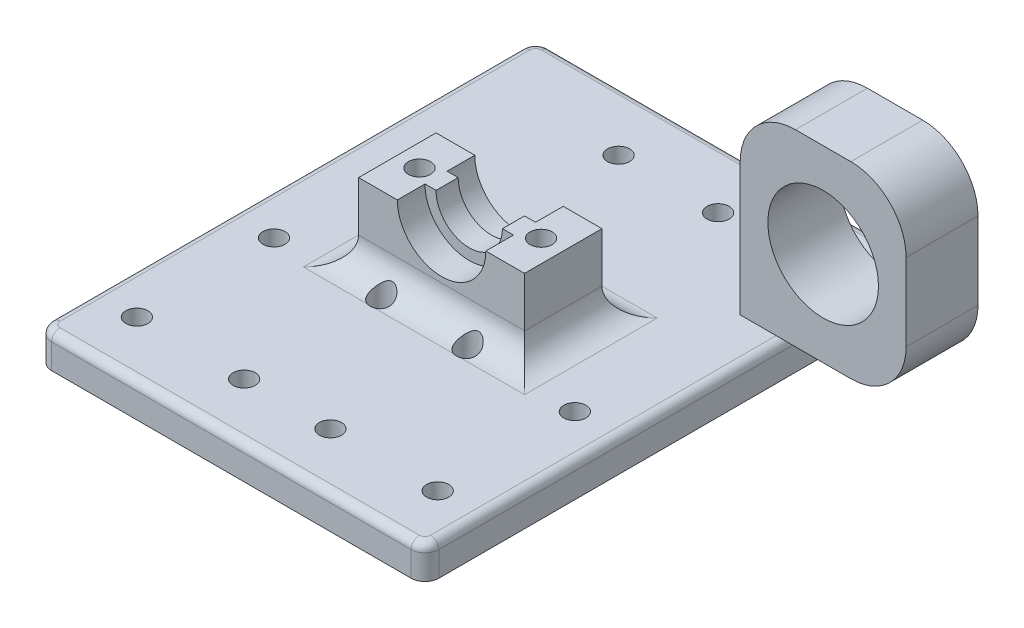
SolidWorks part; units mm, degrees
ref_plane "Front Plane" through (0, 0, 0) normal (0, 0, 1) x (1, 0, 0)
ref_plane "Top Plane" through (0, 0, 0) normal (0, 1, 0) x (1, 0, 0)
ref_plane "Right Plane" through (0, 0, 0) normal (1, 0, 0) x (0, 0, -1)
sketch "Sketch1" plane through (0, 0, 0) normal (0, 1, 0) x (1, 0, 0)
  line L0 (-8.0156, -1.4008) -> (61.9844, -1.4008)
  line L1 (-8.0156, 43.5992) -> (61.9844, 43.5992)
  line L2 (-8.0156, 43.5992) -> (-8.0156, -46.4008)
  line L3 (-8.0156, -46.4008) -> (61.9844, -46.4008)
  line L4 (61.9844, 43.5992) -> (61.9844, -46.4008)
  line L5 (26.9844, 43.5992) -> (26.9844, -46.4008)
  line L6 (9.4844, -1.4008) -> (9.4844, -46.4008)
  line L7 (-8.0156, -23.9008) -> (61.9844, -23.9008)
  circle A0 centre (17.9844, 32.5992) radius 3
  circle A1 centre (17.9844, 32.5992) radius 2
  circle A2 centre (18.095, 8.5992) radius 3
  circle A3 centre (18.095, 8.5992) radius 2
  circle A4 centre (35.8739, 8.5992) radius 2
  circle A5 centre (35.8739, 8.5992) radius 3
  circle A6 centre (35.9844, 32.5992) radius 2
  circle A7 centre (35.9844, 32.5992) radius 3
  circle A8 centre (19.1844, -11.5008) radius 2
  circle A9 centre (19.1844, -11.5008) radius 3
  circle A10 centre (-0.2156, -11.5008) radius 3
  circle A11 centre (-0.2156, -11.5008) radius 2
  circle A12 centre (-0.2156, -36.3008) radius 2
  circle A13 centre (19.1844, -36.3008) radius 3
  circle A14 centre (19.1844, -36.3008) radius 2
  circle A15 centre (-0.2156, -36.3008) radius 3
  circle A16 centre (54.1844, -36.3008) radius 2
  circle A17 centre (54.1844, -36.3008) radius 3
  circle A18 centre (34.7844, -36.3008) radius 2
  circle A19 centre (34.7844, -36.3008) radius 3
  circle A20 centre (34.7844, -11.5008) radius 3
  circle A21 centre (34.7844, -11.5008) radius 2
  circle A22 centre (54.1844, -11.5008) radius 2
  circle A23 centre (54.1844, -11.5008) radius 3
  dimension "D3" = 9
  dimension "D1" = 90
  dimension "D2" = 70
  dimension "D4" = 11
  dimension "D5" = 24
  dimension "D6" = 10.1
  dimension "D7" = 7.8
  dimension "D8" = 17.5
  dimension "D9" = 22.5
extrude "Boss-Extrude1" add sketch "Sketch1" along normal blind 6 contours L5 L1 L2 L0 A2 A0 | L1 L5 L0 L4 A5 A7 | A7 A6 | A0 A1 | A2 A3 | A5 A4 | L7 L6 L3 L5 A13 | L6 L7 L5 L0 A9 | L2 L7 L6 L0 A10 | L5 L7 L4 L0 A20 A23 | L7 L5 L3 L4 A17 A19 | L7 L2 L3 L6 A15 | A10 A11 | A9 A8 | A20 A21 | A23 A22 | A17 A16 | A13 A14 | A15 A12 | A19 | A18 region at (9.1658, 0, -21.1178) region at (0.7344, 0, 1.6858) region at (18.2344, 0, 1.6858) region at (0.7344, 0, 24.1858) region at (44.803, 0, -21.1178) region at (44.4844, 0, 12.7397) region at (18.2344, 0, 24.1858) region at (44.4844, 0, 35.0618) region at (15.0693, 0, -32.5992) region at (15.1799, 0, -8.5992) region at (32.9587, 0, -8.5992) region at (33.0693, 0, -32.5992) region at (16.2693, 0, 11.5008) region at (-3.1307, 0, 11.5008) region at (16.2693, 0, 36.3008) region at (-3.1307, 0, 36.3008) region at (51.2693, 0, 36.3008) region at (31.8693, 0, 11.5008) region at (51.2693, 0, 11.5008)
sketch "Sketch3" plane through (0, 6, 0) normal (0, 1, 0) x (1, 0, 0)
  line L0 (26.9844, 43.5992) -> (26.9844, -46.4008)
  line L1 (11.9844, 5.5992) -> (41.9844, 5.5992)
  line L2 (11.9844, 5.5992) -> (11.9844, -8.4008)
  line L3 (11.9844, -8.4008) -> (41.9844, -8.4008)
  line L4 (41.9844, 5.5992) -> (41.9844, -8.4008)
  line L5 (-8.0156, 43.5992) -> (61.9844, 43.5992) construction
  line L6 (-8.0156, -46.4008) -> (61.9844, -46.4008) construction
  line L7 (-8.0156, -1.4008) -> (61.9844, -1.4008)
  line L8 (-8.0156, 43.5992) -> (-8.0156, -46.4008) construction
  line L9 (61.9844, 43.5992) -> (61.9844, -46.4008) construction
  dimension "D1" = 14
  dimension "D2" = 30
  dimension "D3" = 7
  dimension "D4" = 15
extrude "Boss-Extrude2" add sketch "Sketch3" along normal blind 14 contours L2 L7 L0 L1 | L0 L7 L4 L1 | L7 L0 L3 L4 | L7 L2 L3 L0 region at (34.4844, 6, -2.0992) region at (19.4844, 6, -2.0992) region at (34.4844, 6, 4.9008) region at (19.4844, 6, 4.9008)
fillet "Fillet1" radius 2.5 4 edges at (-8.0156, 3, -43.5992) (61.9844, 3, -43.5992) (61.9844, 3, 46.4008) (-8.0156, 3, 46.4008)
fillet "Fillet2" radius 1.5 8 edges at (26.9844, 6, -43.5992) (-7.2833, 6, 45.6685) (61.2522, 6, 45.6685) (26.9844, 6, 46.4008) (61.2522, 6, -42.867) (61.9844, 6, 1.4008) (-7.2833, 6, -42.867) (-8.0156, 6, 1.4008)
sketch "Sketch4" plane through (0, 20, 0) normal (0, 1, 0) x (1, 0, 0)
  line L0 (26.9844, 42.0992) -> (26.9844, -44.9008)
  line L1 (59.4844, 42.0992) -> (-5.5156, 42.0992) construction
  line L2 (-5.5156, -44.9008) -> (59.4844, -44.9008) construction
  line L3 (-6.5156, -1.4008) -> (60.4844, -1.4008)
  line L4 (-6.5156, 41.0992) -> (-6.5156, -43.9008) construction
  line L5 (60.4844, -43.9008) -> (60.4844, 41.0992) construction
  circle A0 centre (15.9844, -1.4008) radius 2
  circle A1 centre (37.9844, -1.4008) radius 2
  dimension "D1" = 11
extrude "Cut-Extrude1" cut sketch "Sketch4" against normal blind 22 contours L3 A0 | L3 A0 | A1 L3 | A1 L3 region at (15.9844, 20, 0.552) region at (37.9844, 20, 0.552) region at (37.9844, 20, 2.2496) region at (15.9844, 20, 2.2496)
sketch "Sketch5" plane through (0, 0, -5.5992) normal (0, 0, -1) x (-1, 0, 0)
  line L0 (-11.9844, 20) -> (-41.9844, 20) construction
  line L1 (-34.9844, 20) -> (-18.9844, 20)
  circle A0 centre (-26.9844, 20) radius 8
  circle A1 centre (-26.9844, 20) radius 6
extrude "Cut-Extrude2" cut sketch "Sketch5" against normal blind 22 contours A1
sketch "Sketch6" plane through (0, 0, -5.5992) normal (0, 0, -1) x (-1, 0, 0)
  line L0 (-18.9844, 20) -> (-34.9844, 20)
  circle A0 centre (-26.9844, 20) radius 8
  circle A1 centre (-26.9844, 20) radius 6
  circle A2 centre (-26.9844, 20) radius 6
  circle A3 centre (-26.9844, 20) radius 8
  arc M1 (-20.9844, 20) -> (-32.9844, 20) centre (-26.9844, 20) cw
  line M2 (-32.9844, 20) -> (-41.9844, 20)
  line M6 (-11.9844, 20) -> (-20.9844, 20)
  dimension "D1" = 12
  dimension "D2" = 16
extrude "Cut-Extrude4" cut sketch "Sketch6" against normal blind 5 contours A0 M2 M6 M1 region at (26.9844, 12.1789, -5.5992)
sketch "Sketch9" plane through (0, 0, 8.4008) normal (0, 0, 1) x (1, 0, 0)
  circle A0 centre (26.9844, 20) radius 6
  circle A1 centre (26.9844, 20) radius 8
extrude "Cut-Extrude5" cut sketch "Sketch9" against normal blind 5
fillet "Fillet3" radius 5 4 edges at (26.9844, 6, 8.4008) (11.9844, 6, 1.4008) (26.9844, 6, -5.5992) (41.9844, 6, 1.4008)
sketch "Sketch10" plane through (0, 6, 0) normal (0, 1, 0) x (1, 0, 0)
  line L0 (53.9844, 42.0992) -> (53.9844, -44.9008)
  line L1 (59.4844, 42.0992) -> (-5.5156, 42.0992) construction
  line L2 (-5.5156, -44.9008) -> (59.4844, -44.9008) construction
  line L3 (26.9844, 43.5992) -> (26.9844, -46.4008)
  line L4 (-5.5156, 43.5992) -> (59.4844, 43.5992) construction
  line L5 (59.4844, -46.4008) -> (-5.5156, -46.4008) construction
  line L6 (26.9844, -1.4008) -> (60.4844, -1.4008)
  line L7 (53.9844, 31.5992) -> (83.9844, 31.5992)
  line L8 (53.9844, 31.5992) -> (53.9844, 18.5992)
  line L9 (53.9844, 18.5992) -> (83.9844, 18.5992)
  line L10 (83.9844, 31.5992) -> (83.9844, 18.5992)
  line L11 (60.4844, -43.9008) -> (60.4844, 41.0992) construction
  dimension "D1" = 27
  dimension "D2" = 30
  dimension "D3" = 20
  dimension "D4" = 13
extrude "Boss-Extrude5" add sketch "Sketch10" along normal blind 34 contours L7 L10 L9 L8
sketch "Sketch13" plane through (0, 0, -18.5992) normal (0, 0, 1) x (1, 0, 0)
  line L0 (68.9844, 40) -> (68.9844, 6)
  line L1 (53.9844, 40) -> (83.9844, 40) construction
  line L2 (60.4844, 6) -> (83.9844, 6) construction
  line L3 (53.9844, 23) -> (83.9844, 23)
  line L4 (53.9844, 40) -> (53.9844, 6) construction
  line L5 (83.9844, 40) -> (83.9844, 6) construction
  circle A0 centre (68.9844, 23) radius 10
extrude "Cut-Extrude6" cut sketch "Sketch13" against normal blind 34 contours L0 A0 L3 | L3 A0 L0 | L0 A0 L3 | L3 A0 L0 region at (73.2286, 27.2441, -18.5992) region at (64.7403, 27.2441, -18.5992) region at (73.2286, 18.7559, -18.5992) region at (64.7403, 18.7559, -18.5992)
fillet "Fillet5" radius 10 3 edges at (83.9844, 6, -25.0992) (53.9844, 40, -25.0992) (83.9844, 40, -25.0992)
